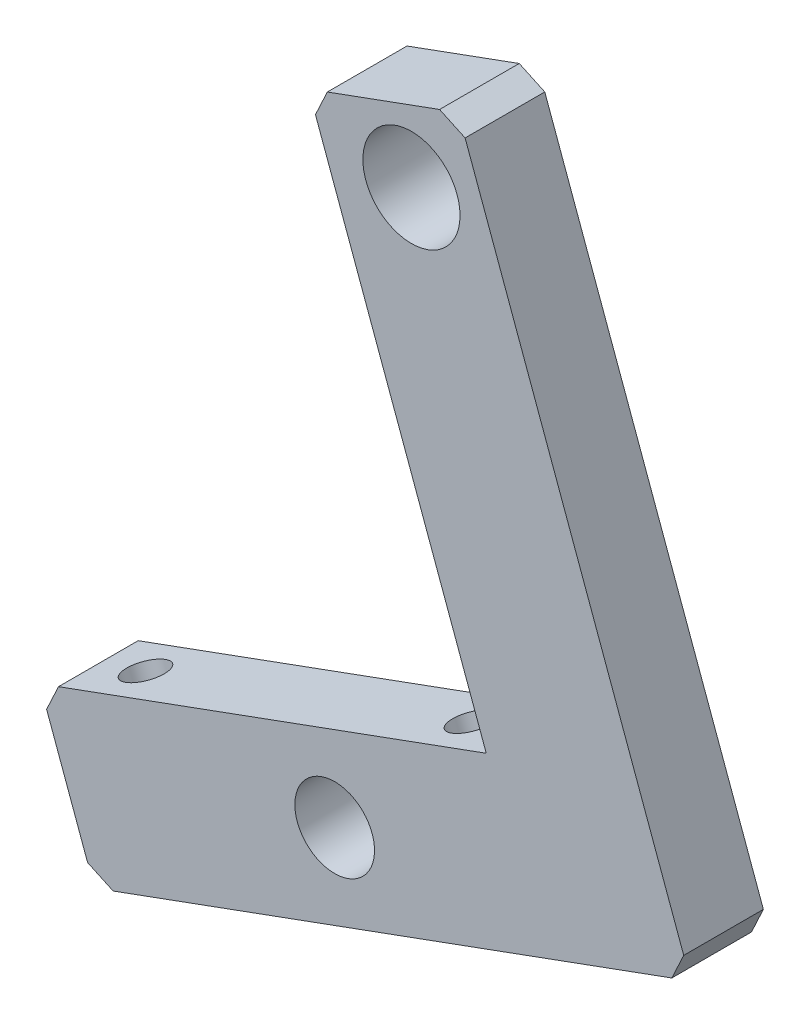
SolidWorks part; units mm, degrees
ref_plane "前基準面" through (0, 0, 0) normal (0, 0, 1) x (1, 0, 0)
ref_plane "上基準面" through (0, 0, 0) normal (0, 1, 0) x (1, 0, 0)
ref_plane "右基準面" through (0, 0, 0) normal (1, 0, 0) x (0, 0, -1)
sketch "草圖1" plane through (0, 0, 0) normal (0, 0, 1) x (1, 0, 0)
  line L0 (-29.9561, 9.7552) -> (-48.7426, 2.8947)
  line L2 (-48.7426, 2.8947) -> (-26.446, -58.1615)
  line L3 (-26.446, -58.1615) -> (-82.4902, -78.6278)
  line L4 (-82.4902, -78.6278) -> (-75.6297, -97.4144)
  line L5 (-75.6297, -97.4144) -> (-0.799, -70.0876)
  line L6 (-0.799, -70.0876) -> (-29.9561, 9.7552)
  circle A0 centre (-35.8357, -1.3461) radius 6.1
  dimension "D4" = 12.2
  dimension "D1" = 20
  dimension "D2" = 20
  dimension "D3" = 65
extrude "填料-伸長1" add sketch "草圖1" along normal blind 10
sketch "草圖2" plane through (15.6286, -42.7967, 0) normal (-0.343, 0.9393, 0) x (0.9393, 0.343, 0)
  circle A0 centre (-95.6715, -4.9822) radius 2.5
  circle A1 centre (-52.1263, -4.9822) radius 2.5
  dimension "D1" = 5
  dimension "D2" = 5
extrude "除料-伸長2" cut sketch "草圖2" against normal through all
chamfer "導角1" distance 2.5 angle 45 5 edges at (-29.9561, 9.7552, 5) (-48.7426, 2.8947, 5) (-0.799, -70.0876, 5) (-75.6297, -97.4144, 5) (-82.4902, -78.6278, 5)
sketch "草圖3" plane through (0, 0, 0) normal (0, 0, -1) x (-1, 0, 0)
  line L0 (152.0261, -114.667) -> (6.0939, -61.3752) construction
  circle A0 centre (45.4703, -75.7548) radius 5
  point P5 (79.06, -88.0211)
extrude "除料-伸長3" cut sketch "草圖3" against normal through all
